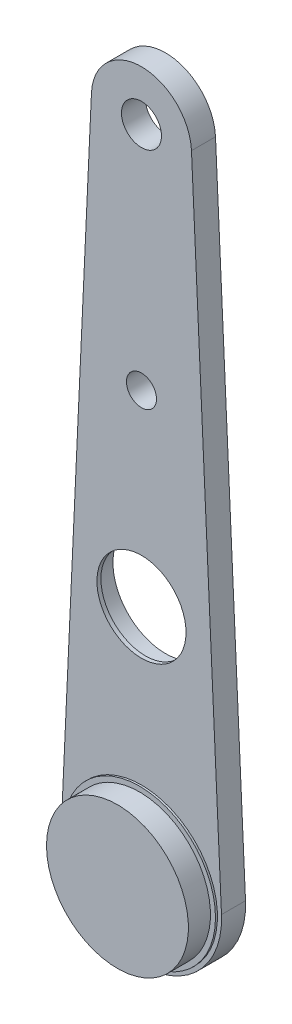
SolidWorks part; units mm, degrees
ref_plane "Front Plane" through (0, 0, 0) normal (0, 0, 1) x (1, 0, 0)
ref_plane "Top Plane" through (0, 0, 0) normal (0, 1, 0) x (1, 0, 0)
ref_plane "Right Plane" through (0, 0, 0) normal (1, 0, 0) x (0, 0, -1)
sketch "Sketch1" plane through (0, 0, 0) normal (0, 0, 1) x (1, 0, 0)
  line L0 (0, 205.4835) -> (0, 0) construction
  line L1 (25.3727, 1.1774) -> (15.8579, 206.2193)
  line L2 (-15.8579, 206.2193) -> (-25.3727, 1.1774)
  circle A1 centre (0, 205.4835) radius 6.35
  arc A2 (-15.8579, 206.2193) -> (15.8579, 206.2193) centre (0, 205.4835) cw
  arc A3 (-25.3727, 1.1774) -> (25.3727, 1.1774) centre (0, 0) ccw
  dimension "D2" = 15.875
  dimension "D3" = 25.4
  dimension "D4" = 12.7
  dimension "D1" = 205.4835
extrude "Boss-Extrude1" add sketch "Sketch1" along normal mid plane 7.62
sketch "Sketch2" plane through (0, 0, 3.81) normal (0, 0, 1) x (1, 0, 0)
  circle A0 centre (0, 0) radius 22.5
  dimension "D1" = 45
extrude "Boss-Extrude2" add sketch "Sketch2" along normal blind 7.62
sketch "Sketch3" plane through (0, 0, 3.81) normal (0, 0, 1) x (1, 0, 0)
  circle A0 centre (0, 0) radius 24.0899
extrude "Boss-Extrude3" add sketch "Sketch3" along normal offset from surface (0.62 mm away) 7 up to face at (22.5, 0, 11.43)
sketch "Sketch4" plane through (0, 0, 3.81) normal (0, 0, 1) x (1, 0, 0)
  circle A0 centre (0, 73.0199) radius 16.6687
  circle A1 centre (0, 132.4635) radius 4.7625
  circle A2 centre (0, 205.4835) radius 6.35 construction
  dimension "D2" = 33.3375
  dimension "D3" = 9.525
  dimension "D1" = 73.0199
  dimension "D4" = 73.0199
extrude "Cut-Extrude1" cut sketch "Sketch4" against normal through all both and the other way through all
sketch "Sketch6" plane through (0, 0, 3.81) normal (0, 0, 1) x (1, 0, 0)
  circle A0 centre (0, 73.0199) radius 16.6687
  circle A1 centre (0, 73.0199) radius 14.1287
  circle A2 centre (0, 73.0199) radius 16.6687 construction
  dimension "D1" = 2.54
extrude "Boss-Extrude4" add sketch "Sketch6" against normal offset from surface (1.27 mm away) 6.35 up to face at (16.6687, 73.0199, -3.81)
sketch "Sketch5" plane through (0, 0, 0) normal (0, 0, 1) x (1, 0, 0)
  line L0 (-155.5635, 72.3706) -> (0, 227.9341)
  line L1 (-155.5635, 72.3706) -> (0, -83.1929)
  line L2 (0, 227.9341) -> (155.5635, 72.3706)
  line L3 (0, -83.1929) -> (155.5635, 72.3706)
  line L4 (-155.5635, 72.3706) -> (155.5635, 72.3706) construction
  line L5 (0, 227.9341) -> (0, -83.1929) construction
  arc A1 (15.8579, 206.2193) -> (-15.8579, 206.2193) centre (0, 205.4835) ccw construction
  point P1 (0, 72.3706)
  dimension "D1" = 220
equation "\"UpperLinkLength\"= \"LowerFirstStage\" + \"LowerSecondStage\""
equation "\"LowerFirstStage\"= \"60T_20T_171B\""
equation "\"LowerSecondStage\"= \"60T_20T_113B\""
equation "\"D1@Sketch1\"=\"UpperLinkLength\""
equation "\"UpperStage\"= \"60T_20T_113B\""
equation "\"60T_20T_113B\"= 2.8748"
equation "\"60T_20T_171B\"= 5.2151"
equation "\"D1@Sketch4\"=\"UpperStage\""
equation "\"D4@Sketch4\"=\"LowerSecondStage\""
